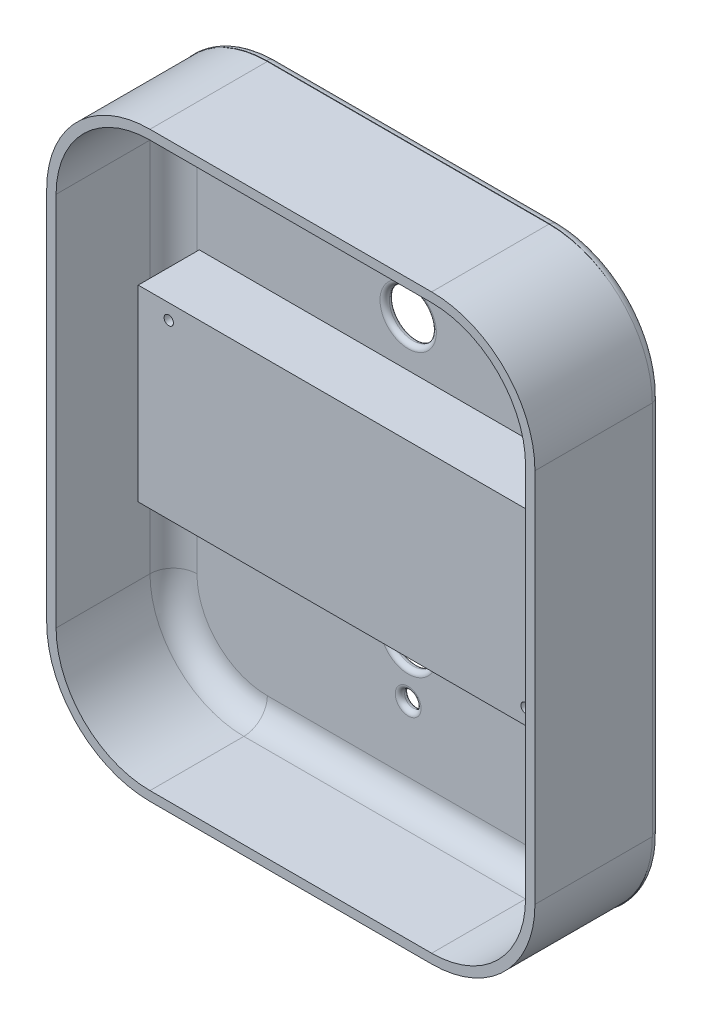
SolidWorks part; units mm, degrees
ref_plane "Front Plane" through (0, 0, 0) normal (0, 0, 1) x (1, 0, 0)
ref_plane "Top Plane" through (0, 0, 0) normal (0, 1, 0) x (1, 0, 0)
ref_plane "Right Plane" through (0, 0, 0) normal (1, 0, 0) x (0, 0, -1)
sketch "Wall Backing" plane through (0, 0, 0) normal (0, 0, 1) x (1, 0, 0)
  line L1 (-37.5, 55) -> (37.5, 55)
  line L2 (-37.5, 55) -> (-37.5, -55)
  line L3 (-37.5, -55) -> (37.5, -55)
  line L4 (37.5, 55) -> (37.5, -55)
  line L5 (-28.5, 50) -> (28.5, 50)
  line L6 (-28.5, 50) -> (-28.5, -50)
  line L7 (-28.5, -50) -> (28.5, -50)
  line L8 (28.5, 50) -> (28.5, -50)
  point P4 (-37.5, 0)
  point P6 (0, 55)
  point P11 (0, 50)
  point P12 (-28.5, 0)
  dimension "D1" = 75
  dimension "D2" = 110
  dimension "D3" = 57
  dimension "D4" = 100
sketch "Case Sides" plane through (0, 0, 0) normal (0, 0, 1) x (1, 0, 0)
  line L0 (0, 60) -> (0, -60) construction
  line L5 (-30, 60) -> (30, 60)
  line L6 (-50, 40) -> (-50, -40)
  line L7 (-30, -60) -> (30, -60)
  line L8 (50, 40) -> (50, -40)
  line L9 (-50, 0) -> (50, 0) construction
  line L10 (-30, 62) -> (30, 62)
  line L11 (52, 40) -> (52, -40)
  line L12 (-30, -62) -> (30, -62)
  line L13 (-52, 40) -> (-52, -40)
  arc A2 (50, 40) -> (30, 60) centre (30, 40) ccw
  arc A3 (50, -40) -> (30, -60) centre (30, -40) cw
  arc A4 (-30, -60) -> (-50, -40) centre (-30, -40) cw
  arc A5 (-50, 40) -> (-30, 60) centre (-30, 40) cw
  arc A6 (52, 40) -> (30, 62) centre (30, 40) ccw
  arc A7 (52, -40) -> (30, -62) centre (30, -40) cw
  arc A8 (-30, -62) -> (-52, -40) centre (-30, -40) cw
  arc A9 (-52, 40) -> (-30, 62) centre (-30, 40) cw
  point P17 (50, 60)
  point P23 (-50, -60)
  point P26 (-50, 60)
  dimension "D5" = 20
  dimension "D3" = 100
  dimension "D4" = 120
  dimension "D6" = 2
sketch "Case Bottom" plane through (0, 0, 0) normal (0, 0, 1) x (1, 0, 0)
  line L0 (-30.1664, 62.1012) -> (30.1664, 62.1012)
  line L1 (51.8136, 39.8409) -> (51.8136, -39.8409)
  line L2 (-30.2679, -61.8723) -> (30.2679, -61.8723)
  line L3 (-52.1862, 40.0195) -> (-52.1862, -40.0195)
  line L4 (0, 41) -> (0, 0) construction
  line L5 (0, 0) -> (0, -41) construction
  line L6 (0, -30) -> (0, 0) construction
  line L7 (0, 30) -> (0, 0) construction
  arc A0 (51.8136, 39.8409) -> (30.1664, 62.1012) centre (29.8858, 40.1727) ccw
  arc A1 (51.8136, -39.8409) -> (30.2679, -61.8723) centre (30.6332, -40.6785) cw
  arc A2 (-30.2679, -61.8723) -> (-52.1862, -40.0195) centre (-30.5767, -40.2636) cw
  arc A3 (-52.1862, 40.0195) -> (-30.1664, 62.1012) centre (-29.8045, 39.7205) cw
  circle A4 centre (0, 41) radius 1.75
  circle A5 centre (0, -41) radius 1.75
  circle A6 centre (0, 30) radius 5
  circle A7 centre (0, -30) radius 5
  point P21 (0, 0)
  point P22 (0, 0)
  point P23 (0, 62.1012)
  point P24 (0, -61.8723)
  point P25 (-52.1862, 0)
  point P26 (51.8136, 0)
  point P28 (0, 0)
  point P29 (0, 0)
  dimension "D2" = 3.5
  dimension "D3" = 10
  dimension "D1" = 82
  dimension "D4" = 30
  dimension "D5" = 104
extrude "Boss-Extrude7" add sketch "Case Sides" along normal blind 25
extrude "Boss-Extrude9" add sketch "Case Bottom" against normal blind 2
sketch "Sonoff" plane through (0, 0, 0) normal (0, 0, 1) x (1, 0, 0)
  line L0 (-44.5, -20) -> (-44.5, 20)
  line L1 (-44.5, -20) -> (44.5, -20)
  line L2 (44.5, -20) -> (44.5, 20)
  line L3 (-44.5, 20) -> (44.5, 20)
  line L4 (-44.5, 0) -> (44.5, 0) construction
  line L5 (0, 20) -> (0, -20) construction
  line L6 (-38, 16.75) -> (-38, 0) construction
  line L7 (38, -16.75) -> (38, 0) construction
  line L8 (-38, 16.75) -> (0, 16.75) construction
  line L9 (38, -16.75) -> (0, -16.75) construction
  circle A3 centre (-38, 16.75) radius 1
  circle A4 centre (38, -16.75) radius 1
  dimension "D5" = 2
  dimension "D1" = 89
  dimension "D2" = 40
  dimension "D3" = 76
  dimension "D4" = 33.5
fillet "Fillet1" radius 5 8 edges at (0, -60, 0) (-44.1421, -54.1421, 0) (-50, 0, 0) (-44.1421, 54.1421, 0) (0, 60, 0) (44.1421, 54.1421, 0) (50, 0, 0) (44.1421, -54.1421, 0)
fillet "Fillet2" radius 2 8 edges at (51.8136, 0, -2) (45.6079, 55.4618, -2) (0, 62.1012, -2) (-45.6544, 55.5259, -2) (45.7878, -55.4991, -2) (0, -61.8723, -2) (-45.835, -55.5677, -2) (-52.1862, 0, -2)
fillet "Fillet3" radius 1 8 edges at (1.75, -41, -2) (1.75, -41, 0) (5, -30, -2) (5, -30, 0) (5, 30, 0) (5, 30, -2) (1.75, 41, 0) (1.75, 41, -2)
extrude "Boss-Extrude10" add sketch "Sonoff" along normal blind 13
